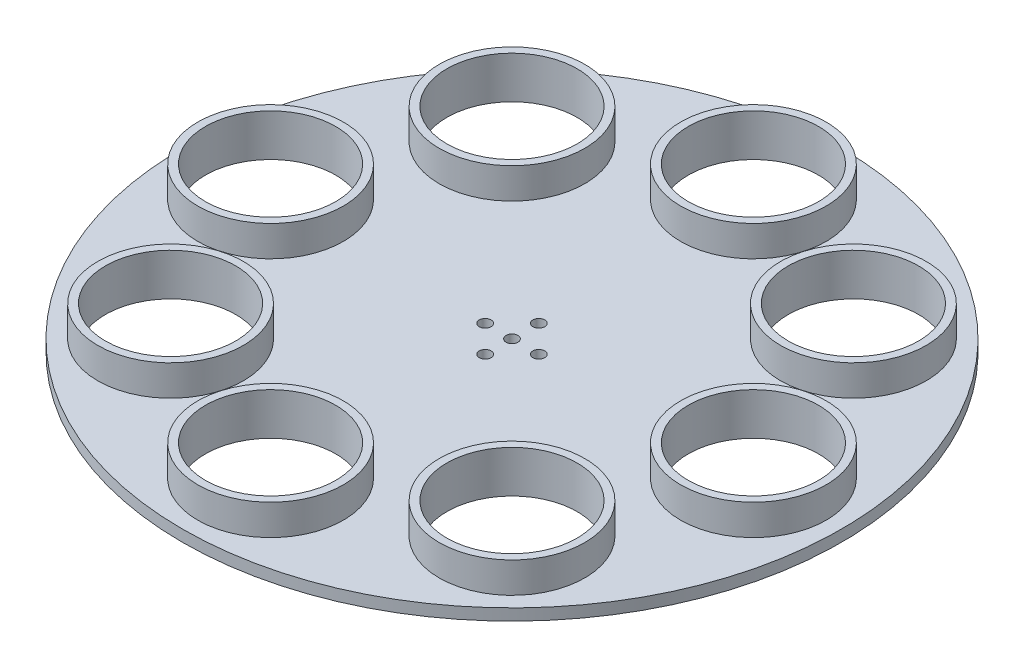
SolidWorks part; units mm, degrees
ref_plane "前视基准面" through (0, 0, 0) normal (0, 0, 1) x (1, 0, 0)
ref_plane "上视基准面" through (0, 0, 0) normal (0, 1, 0) x (1, 0, 0)
ref_plane "右视基准面" through (0, 0, 0) normal (1, 0, 0) x (0, 0, -1)
other "Configuration Table"
sketch "草图1" plane through (0, 0, 0) normal (0, 1, 0) x (1, 0, 0)
  circle A0 centre (0, 0) radius 86
  circle A3 centre (0, 63) radius 17
  circle A4 centre (-63, 0) radius 17
  circle A5 centre (0, -63) radius 17
  circle A6 centre (63, 0) radius 17
  circle A7 centre (-44.5443, 44.5443) radius 17
  circle A8 centre (-44.5477, -44.5477) radius 17
  circle A9 centre (44.5477, 44.5477) radius 17
  circle A10 centre (44.5477, -44.5477) radius 17
  circle A11 centre (0, 0) radius 1.55
  circle A12 centre (0, 7) radius 1.55
  circle A13 centre (7, 0) radius 1.55
  circle A14 centre (-7, 0) radius 1.55
  circle A15 centre (0, -7) radius 1.55
  circle A16 centre (-44.5443, 44.5443) radius 19
  circle A17 centre (0, 63) radius 19
  circle A18 centre (44.5477, 44.5477) radius 19
  circle A19 centre (63, 0) radius 19
  circle A20 centre (44.5477, -44.5477) radius 19
  circle A21 centre (0, -63) radius 19
  circle A22 centre (-44.5477, -44.5477) radius 19
  circle A23 centre (-63, 0) radius 19
  point P18 (33.5849, 33.5849)
  point P20 (-63, 0)
  point P21 (0, 63)
sketch "草图2" plane through (0, 0, 0) normal (0, 1, 0) x (1, 0, 0)
sketch "草图3" plane through (0, 0, 0) normal (0, 1, 0) x (1, 0, 0)
sketch "草图4" plane through (0, 0, 0) normal (0, 1, 0) x (1, 0, 0)
extrude "凸台-拉伸2" add sketch "草图1" along normal blind 11 contours A23 A4 | A22 A8 | A21 A5 | A20 A10 | A19 A6 | A17 A3 | A18 A9 | A16 A7 region at (-63.0069, 0, -44.5443) region at (-18.4626, 0, -63) region at (26.0851, 0, -44.5477) region at (44.5374, 0, 0) region at (26.0851, 0, 44.5477) region at (-18.4626, 0, 63) region at (-63.0103, 0, 44.5477) region at (-81.4626, 0, 0)
extrude "凸台-拉伸3" add sketch "草图1<8>" along normal blind 3 contours A0 A23 A22 A21 A20 A19 A18 A17 A16 A15 A14 A13 A12 A11 region at (-83.5676, 0, 0)
sketch "草图1<8>" plane through (0, 0, 0) normal (0, 1, 0) x (1, 0, 0) same geometry as "草图1"
